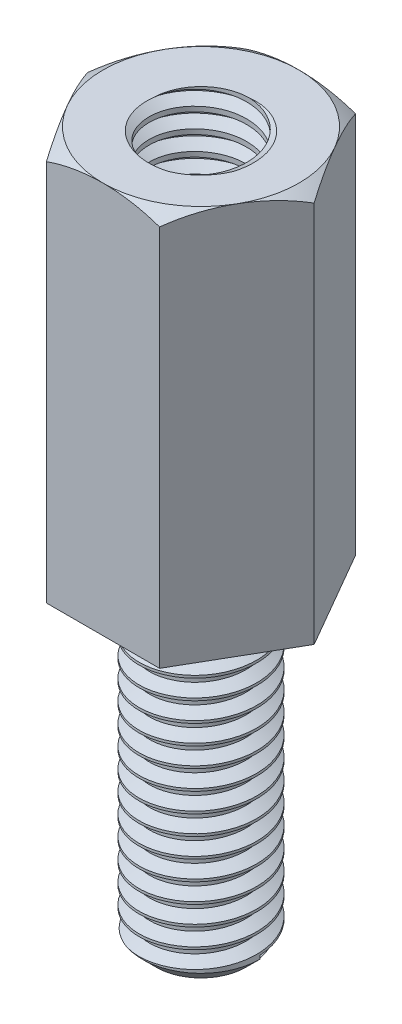
SolidWorks part; units mm, degrees
ref_plane "Front Plane" through (0, 0, 0) normal (0, 0, 1) x (1, 0, 0)
ref_plane "Top Plane" through (0, 0, 0) normal (0, 1, 0) x (1, 0, 0)
ref_plane "Right Plane" through (0, 0, 0) normal (1, 0, 0) x (0, 0, -1)
sketch "Sketch2" plane through (0, 0, 0) normal (0, 1, 0) x (1, 0, 0)
  line L1 (2.8868, 0) -> (1.4434, 2.5)
  line L2 (1.4434, 2.5) -> (-1.4434, 2.5)
  line L3 (-1.4434, 2.5) -> (-2.8868, 0)
  line L4 (-2.8868, 0) -> (-1.4434, -2.5)
  line L5 (-1.4434, -2.5) -> (1.4434, -2.5)
  line L6 (1.4434, -2.5) -> (2.8868, 0)
  circle A0 centre (0, 0) radius 2.5 construction
  dimension "D1" = 5
extrude "Boss-Extrude1" add sketch "Sketch2" along normal blind 10
sketch "Sketch3" plane through (0, 10, 0) normal (0, 1, 0) x (1, 0, 0)
  circle A0 centre (0, 0) radius 1.25
  dimension "D1" = 2.5
extrude "Cut-Extrude1" cut sketch "Sketch3" against normal blind 8
thread "Thread1" pitch 0.5 method cut profile "Thread Profile1" start angle 0, offset 1, length 9, pitch 0.5, diameter 2.5
ref_plane "Plane1" through (-1.25, 11, 0) normal (0, 0, 1) x (-1, 0, 0)
sketch "Thread Profile1" plane through (-1.25, 11, 0) normal (0, 0, 1) x (-1, 0, 0)
  line L0 (0, 0) -> (0, 0.5) construction
  line L1 (0, 0) -> (0.2706, 0.1562)
  line L2 (0.2706, 0.1562) -> (0.2706, 0.2187)
  line L3 (0.2706, 0.2187) -> (0, 0.375)
  line L4 (0.2706, 0.1875) -> (0, 0.1875) construction
  line L11 (0, 0) -> (0, 0.375)
  point P2 (0, 0)
  dimension "Pitch" = 0.5
  dimension "Profile_Angle" = 60
  dimension "Profile_Land" = 0.0625
  dimension "Profile_Height" = 0.2706
ref_axis "Axis1" through (0, -8.9103, 0) along (0, 1, 0)
sketch "Sketch11" plane through (0, 0, 0) normal (0, 1, 0) x (1, 0, 0)
  circle A0 centre (0, 0) radius 1.5
  dimension "D1" = 3
extrude "Boss-Extrude2" add sketch "Sketch11" against normal blind 8
cosmetic thread "Cosmetic Thread2" parameters "D1"=9, "D2"=2
thread "Thread2" pitch 0.5 method cut profile "Thread Profile2" start angle 0, offset 0, length 7.5, pitch 0.5, diameter 3
ref_plane "Plane2" through (1.5, -8, 0) normal (0, 0, 1) x (1, 0, 0)
sketch "Thread Profile2" plane through (1.5, -8, 0) normal (0, 0, 1) x (1, 0, 0)
  line L0 (0, 0) -> (0, 0.5) construction
  line L11 (0, 0) -> (0, 0.4375)
  line L12 (0, 0.4375) -> (-0.2706, 0.2812)
  line L13 (-0.2706, 0.2812) -> (-0.2706, 0.1562)
  line L15 (-0.2706, 0.1562) -> (0, 0)
  line L17 (-0.2706, 0.2187) -> (0, 0.2187) construction
  point P2 (0, 0)
  dimension "Pitch" = 0.5
  dimension "Profile_Angle" = 60
  dimension "Profile_Land" = 0.125
  dimension "Profile_Height" = 0.2706
sketch "Sketch10" plane through (0, 0, 0) normal (1, 0, 0) x (0, 0, -1)
  line L0 (-3.5, 9.2406) -> (-3.5, 10)
  line L1 (-3.5, 10) -> (-2.5, 10)
  line L3 (-2.15, -8) -> (-1.15, -8)
  line L4 (-1.15, -8) -> (-2.15, -7)
  line L5 (-2.15, -7) -> (-2.15, -8)
  line L7 (-1.2, 0) -> (-4, 0)
  line L8 (-1.2, 0) -> (-1.2, -0.5)
  line L9 (-1.2, -0.5) -> (-4, -3.3)
  line L10 (-4, 0) -> (-4, -3.3)
  arc A0 (-2.5, 10) -> (-3.5, 9.2406) centre (0, 5.6699) ccw
  dimension "D1" = 5
  dimension "D2" = 1
  dimension "D3" = 10
  dimension "D4" = 2.5
  dimension "D5" = 45
  dimension "D6" = 8
  dimension "D7" = 1
  dimension "D8" = 2.15
  dimension "D9" = 4
  dimension "D10" = 1.2
  dimension "D11" = 135
  dimension "D12" = 0.5
revolve "Cut-Revolve1" cut sketch "Sketch10" angle 360 about axis through (0, -8.9103, 0) along (0, 1, 0)
equation "\"Stud length\" = 8"
equation "\"Hex Length\"= 10"
equation "\"Internal gap\"= 2"
equation "\"D1@Boss-Extrude1\"=\"Hex Length\""
equation "\"D1@Cut-Extrude1\"=\"Hex Length\"-\"Internal gap\""
equation "\"D4@Thread1\"=\"Hex Length\"-\"Internal gap\"+1"
equation "\"D1@Boss-Extrude2\"=\"Stud length\""
equation "\"D3@Sketch10\"=\"Hex Length\""
equation "\"D6@Sketch10\"=\"Stud length\""
equation "\"D4@Thread2\"=\"Stud length\"-0.5"
